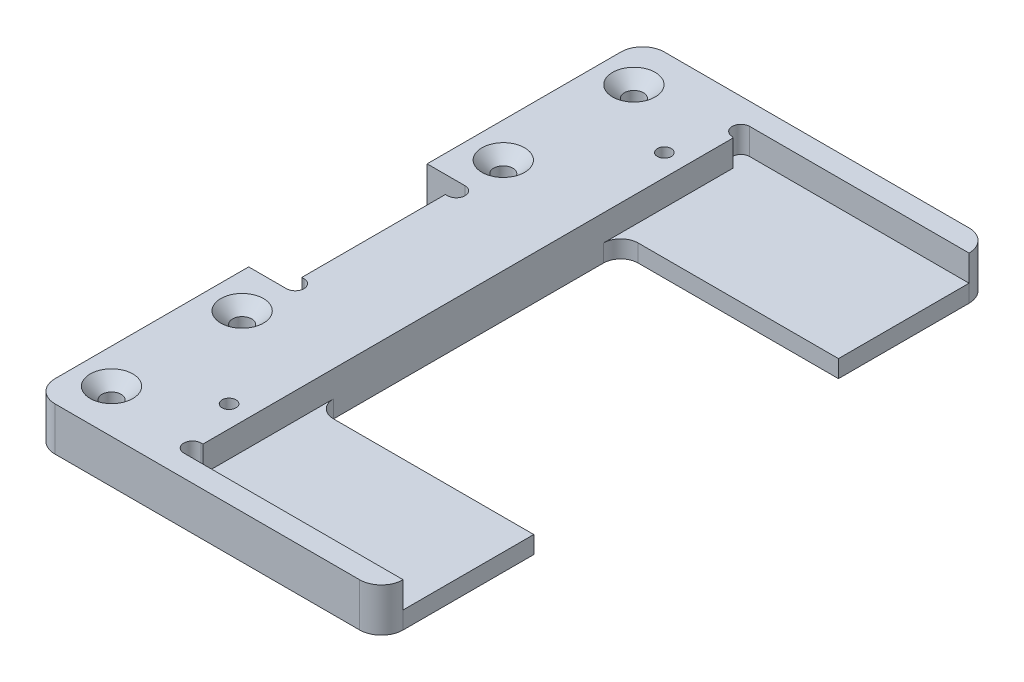
SolidWorks part; units mm, degrees
material "7075-T6 (SN)"
ref_plane "Front Plane" through (0, 0, 0) normal (0, 0, 1) x (1, 0, 0)
ref_plane "Top Plane" through (0, 0, 0) normal (0, 1, 0) x (1, 0, 0)
ref_plane "Right Plane" through (0, 0, 0) normal (1, 0, 0) x (0, 0, -1)
sketch "Sketch1" plane through (0, 0, 0) normal (0, 1, 0) x (1, 0, 0)
  line L0 (0, 35) -> (0, 10.25)
  line L1 (0, 10.25) -> (4.1, 10.25)
  line L2 (4.1, 10.25) -> (4.1, -10.25)
  line L3 (4.1, -10.25) -> (0, -10.25)
  line L4 (0, -10.25) -> (0, -35)
  line L5 (0, -35) -> (40, -35)
  line L6 (40, -35) -> (40, -17.5)
  line L7 (40, -17.5) -> (15, -17.5)
  line L8 (15, -17.5) -> (15, 17.5)
  line L9 (15, 17.5) -> (40, 17.5)
  line L10 (40, 17.5) -> (40, 35)
  line L11 (40, 35) -> (0, 35)
  point P0 (4.1, 0)
  point P15 (15, 0)
  dimension "D1" = 4.1
  dimension "D2" = 70
  dimension "D3" = 20.5
  dimension "D4" = 25
  dimension "D5" = 15
  dimension "D6" = 17.5
extrude "Boss-Extrude1" add sketch "Sketch1" along normal blind 5
fillet "Fillet1" radius 2 2 edges at (15, 2.5, 17.5) (15, 2.5, -17.5)
fillet "Fillet2" radius 2.5 4 edges at (0, 2.5, -35) (0, 2.5, 35) (40, 2.5, -35) (40, 2.5, 35)
sketch "Sketch3" plane through (0, 5, 0) normal (0, 1, 0) x (1, 0, 0)
  line L0 (4.1, 10.25) -> (4.35, 10.25)
  line L1 (4.35, 8.25) -> (4.1, 8.25)
  line L2 (4.1, 10.25) -> (4.1, -10.25) construction
  line L3 (4.1, 8.25) -> (4.1, 10.25)
  line L4 (4.1, -10.25) -> (4.1, -8.25)
  line L5 (4.1, -8.25) -> (4.35, -8.25)
  line L6 (4.35, -10.25) -> (4.1, -10.25)
  arc A0 (4.35, 10.25) -> (4.35, 8.25) centre (4.35, 9.25) cw
  arc A1 (4.35, -8.25) -> (4.35, -10.25) centre (4.35, -9.25) cw
  dimension "D1" = 1
  dimension "D2" = 0.25
extrude "Cut-Extrude2" cut sketch "Sketch3" against normal up to next
hole_wizard "CSK for M2 Countersunk Flat Head Screw1" positions "Sketch4" profile "Sketch5" countersink size "M2" standard "DIN" end condition up to next
sketch "Sketch4" plane through (0, 5, 0) normal (0, 1, 0) x (1, 0, 0)
  line L0 (2.5, -35) -> (37.5, -35) construction
  line L1 (37.5, 35) -> (2.5, 35) construction
  line L2 (0, 32.5) -> (0, 10.25) construction
  point P0 (4, 30)
  point P2 (4, 15)
  point P4 (4, -15)
  point P6 (4, -30)
  dimension "D1" = 5
  dimension "D2" = 15
  dimension "D3" = 15
  dimension "D4" = 5
  dimension "D5" = 4
sketch "Sketch5" plane through (4, 5, -30) normal (1, 0, 0) x (0, 0, 1)
  line L0 (0, 0) -> (0, 5)
  line L1 (0, 5) -> (1.1, 5)
  line L2 (1.1, 5) -> (1.1, 1.35)
  line L3 (1.1, 1.35) -> (2.45, 0)
  line L5 (2.45, 0) -> (0, 0)
  line L6 (-1.1, 1.35) -> (-2.45, 0) construction
  line L11 (0, -6.35) -> (0, 107.95) construction
  dimension "Thru Hole Dia." = 2.2
  dimension "Thru Hole Depth" = 5
  dimension "Near C'Sink Dia." = 4.9
  dimension "Near C'Sink Angle" = 90
hole_wizard "M2 Tapped Hole1" positions "Sketch6" profile "Sketch8" tap size "M2" standard "DIN" end condition up to next
sketch "Sketch6" plane through (0, 5, 0) normal (0, 1, 0) x (1, 0, 0)
  line L0 (0, 32.5) -> (0, 10.25) construction
  line L1 (37.5, 35) -> (2.5, 35) construction
  line L2 (2.5, -35) -> (37.5, -35) construction
  point P0 (12.5, -25)
  point P2 (12.5, 25)
  dimension "D1" = 12.5
  dimension "D2" = 10
  dimension "D3" = 10
sketch "Sketch8" plane through (12.5, 5, 25) normal (1, 0, 0) x (0, 0, 1)
  line L0 (0, 0) -> (0, 5)
  line L1 (0, 5) -> (0.8, 5)
  line L2 (0.8, 5) -> (0.8, 0)
  line L5 (0.8, 0) -> (0, 0)
  line L11 (0, -6.35) -> (0, 107.95) construction
  dimension "Thru Tap Drill Dia." = 1.6
  dimension "Thru Tap Drill Depth" = 5
cosmetic thread "Hole Thread1" parameters "D2"=2
cosmetic thread "Hole Thread2" parameters "D2"=2
sketch "Sketch9" plane through (0, 5, 0) normal (0, 1, 0) x (1, 0, 0)
  line L7 (40, 17.5) -> (40, 32.5) construction
  line L8 (14.8, 32.5) -> (40, 32.5)
  line L9 (14.8, 32.5) -> (14.8, 20)
  line L10 (14.8, 20) -> (40, 20)
  line L11 (40, 32.5) -> (40, 20)
  line L15 (40, -32.5) -> (14.8, -32.5)
  line L16 (40, -32.5) -> (40, -20)
  line L17 (40, -20) -> (14.8, -20)
  line L18 (14.8, -32.5) -> (14.8, -20)
  dimension "D1" = 12.5
  dimension "D2" = 25.2
extrude "Cut-Extrude3" cut sketch "Sketch9" against normal blind 1.25
sketch "Sketch10" plane through (0, 5, 0) normal (0, 1, 0) x (1, 0, 0)
  line L0 (14.8, 32.5) -> (14.8, 20) construction
  line L1 (14.8, 32.5) -> (14.8, 20) construction
  line L2 (14.8, 22) -> (14.8, 20)
  line L3 (14.8, 30.5) -> (14.8, 32.5)
  arc A0 (14.8, 32.5) -> (14.8, 30.5) centre (14.8, 31.5) ccw
  arc A1 (14.8, 20) -> (14.8, 22) centre (14.8, 21) cw
  dimension "D1" = 2
extrude "Cut-Extrude4" cut sketch "Sketch10" against normal up to surface (1.25 mm away) up to face at (27.4, 3.75, -26.25)
ref_plane "Plane1" through (0, 2.5, 0) normal (0, -1, 0) x (-1, 0, 0)
mirror "Mirror1" about plane through (0, 2.5, 0) normal (0, -1, 0) of "CSK for M2 Countersunk Flat Head Screw1"
mirror "Mirror2" about plane through (0, 0, 0) normal (0, 0, 1) of "Cut-Extrude4"
sketch "Sketch11" plane through (0, 5, 0) normal (0, 1, 0) x (1, 0, 0)
  line L1 (15, 15.5) -> (40, 15.5)
  line L2 (15, 15.5) -> (15, 20)
  line L3 (15, 20) -> (40, 20)
  line L4 (40, 15.5) -> (40, 20)
  line L5 (15, -15.5) -> (40, -15.5)
  line L6 (15, -15.5) -> (15, -20)
  line L7 (15, -20) -> (40, -20)
  line L8 (40, -15.5) -> (40, -20)
extrude "Cut-Extrude5" cut sketch "Sketch11" against normal up to surface (1.25 mm away) up to face at (22.8667, 3.75, -26.25)
sketch "Sketch12" plane through (0, 3.75, 0) normal (0, 1, 0) x (1, 0, 0)
  line L2 (14.8, 20) -> (15, 20)
  line L3 (14.8, 22) -> (14.8, 30.5)
  line L4 (14.8, 30.5) -> (15, 30.3726)
  line L5 (15, 30.3726) -> (15, 20)
  line L6 (14.8, -20) -> (15, -20)
  line L7 (14.8, -22) -> (14.8, -30.5)
  line L8 (14.8, -30.5) -> (15, -30.5)
  line L9 (15, -30.5) -> (15, -20)
  arc A4 (14.8, -20) -> (14.8, -22) centre (14.8, -21) ccw construction
  arc A5 (14.8, 22) -> (14.8, 20) centre (14.8, 21) ccw construction
  arc A6 (14.8, -20) -> (14.8, -22) centre (14.8, -21) ccw
  arc A7 (14.8, 22) -> (14.8, 20) centre (14.8, 21) ccw
extrude "Boss-Extrude2" add sketch "Sketch12" along normal up to surface (1.25 mm away) up to face at (12.7692, 5, 0)
sketch "Sketch13" plane through (0, 3.75, 0) normal (0, 1, 0) x (1, 0, 0)
  line L5 (14.8, 30.5) -> (15, 30.3726)
  line L6 (15, 30.3726) -> (15, 15.5)
  line L7 (17, 17.5) -> (40, 17.5)
  line L8 (40, 17.5) -> (40, 32.5)
  line L9 (40, 32.5) -> (14.8, 32.5)
  line L10 (14.8, 30.5) -> (15, 30.3726)
  line L11 (15, 30.3726) -> (15, 15.5)
  line L12 (17, 17.5) -> (40, 17.5)
  line L13 (40, 17.5) -> (40, 32.5)
  line L14 (40, 32.5) -> (14.8, 32.5)
  line L15 (15, -15.5) -> (15, -30.5)
  line L16 (15, -30.5) -> (14.8, -30.5)
  line L17 (14.8, -32.5) -> (40, -32.5)
  line L18 (40, -32.5) -> (40, -17.5)
  line L19 (40, -17.5) -> (17, -17.5)
  line L20 (15, -15.5) -> (15, -30.5)
  line L21 (15, -30.5) -> (14.8, -30.5)
  line L22 (14.8, -32.5) -> (40, -32.5)
  line L23 (40, -32.5) -> (40, -17.5)
  line L24 (40, -17.5) -> (17, -17.5)
  arc A2 (14.8, 32.5) -> (14.8, 30.5) centre (14.8, 31.5) ccw
  arc A3 (17, 17.5) -> (15, 15.5) centre (17, 15.5) ccw
  arc A4 (14.8, 32.5) -> (14.8, 30.5) centre (14.8, 31.5) ccw
  arc A5 (17, 17.5) -> (15, 15.5) centre (17, 15.5) ccw
  arc A6 (14.8, -30.5) -> (14.8, -32.5) centre (14.8, -31.5) ccw
  arc A7 (15, -15.5) -> (17, -17.5) centre (17, -15.5) ccw
  arc A8 (14.8, -30.5) -> (14.8, -32.5) centre (14.8, -31.5) ccw
  arc A9 (15, -15.5) -> (17, -17.5) centre (17, -15.5) ccw
  dimension "D1" = 0
  dimension "D2" = 0
extrude "Cut-Extrude6" cut sketch "Sketch13" against normal offset from surface (1.75 mm away) 2 up to face at (4, 0, -32.45)
